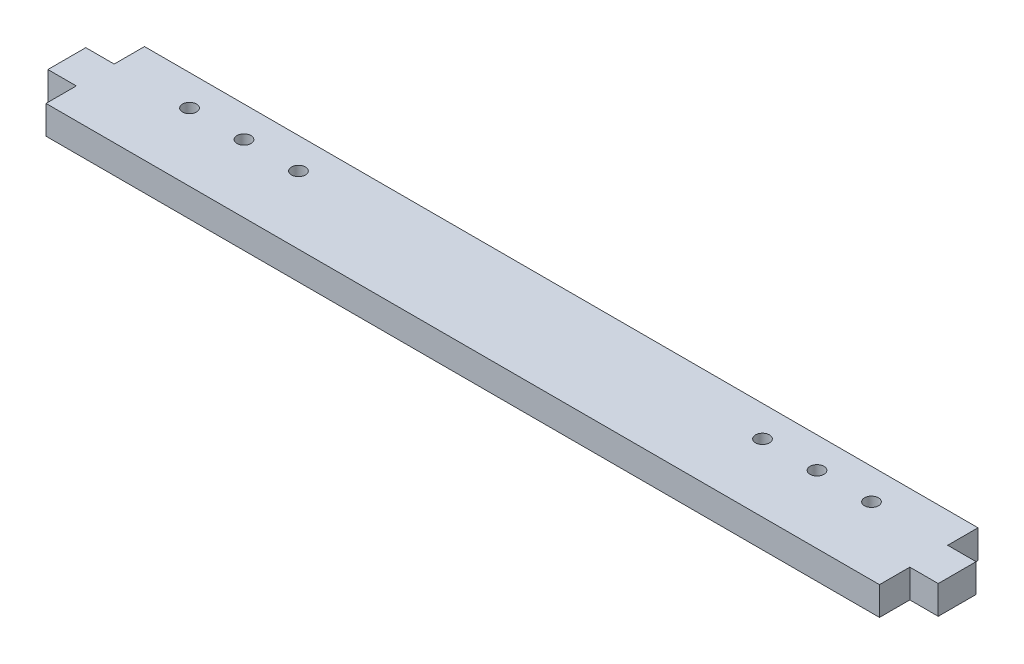
SolidWorks part; units mm, degrees
ref_plane "Front Plane" through (0, 0, 0) normal (0, 0, 1) x (1, 0, 0)
ref_plane "Top Plane" through (0, 0, 0) normal (0, 1, 0) x (1, 0, 0)
ref_plane "Right Plane" through (0, 0, 0) normal (1, 0, 0) x (0, 0, -1)
sketch "Sketch1" plane through (0, 0, 0) normal (0, 1, 0) x (1, 0, 0)
  line L1 (139.7, -16.51) -> (-139.7, -16.51)
  line L2 (139.7, -16.51) -> (139.7, 16.51)
  line L3 (139.7, 16.51) -> (-139.7, 16.51)
  line L4 (-139.7, -16.51) -> (-139.7, 16.51)
  line L5 (139.7, -16.51) -> (-139.7, 16.51) construction
  line L6 (139.7, 16.51) -> (-139.7, -16.51) construction
  point P0 (0, 0)
  dimension "D1" = 279.4
  dimension "D2" = 33.02
extrude "Boss-Extrude1" add sketch "Sketch1" along normal blind 9.525
sketch "Sketch2" plane through (139.7, 0, 0) normal (1, 0, 0) x (0, 0, -1)
  line L0 (-16.51, 0) -> (16.51, 0) construction
  line L1 (-6.35, 0) -> (6.35, 0)
  line L2 (-6.35, 0) -> (-6.35, 9.525)
  line L3 (-6.35, 9.525) -> (6.35, 9.525)
  line L4 (6.35, 0) -> (6.35, 9.525)
  line L5 (-16.51, 9.525) -> (16.51, 9.525) construction
  line L6 (-16.51, 9.525) -> (-16.51, 0) construction
  dimension "D1" = 12.7
  dimension "D2" = 10.16
extrude "Boss-Extrude2" add sketch "Sketch2" along normal blind 9.525
mirror "Mirror1" about plane through (0, 0, 0) normal (1, 0, 0) of "Boss-Extrude2"
sketch "Sketch3" plane through (0, 0, 0) normal (0, -1, 0) x (1, 0, 0)
  line L0 (139.7, -6.35) -> (139.7, -16.51) construction
  line L1 (139.7, -16.51) -> (-139.7, -16.51) construction
  line L2 (114.3, -16.51) -> (77.7748, -16.51) construction
  line L3 (114.3, -16.51) -> (114.3, -6.1976) construction
  line L4 (114.3, -6.1976) -> (77.7748, -6.1976) construction
  line L5 (77.7748, -16.51) -> (77.7748, -6.1976) construction
  line L6 (114.3, -16.51) -> (77.7748, -6.1976) construction
  line L7 (114.3, -6.1976) -> (77.7748, -16.51) construction
  circle A0 centre (114.3, -6.1976) radius 2.3368
  circle A1 centre (77.7748, -6.1976) radius 2.3368
  circle A2 centre (96.0374, -6.1976) radius 2.3368
  point P6 (96.0374, -11.3538)
  dimension "D4" = 4.6736
  dimension "D5" = 4.6736
  dimension "D6" = 4.6736
  dimension "D1" = 36.5252
  dimension "D2" = 10.3124
  dimension "D3" = 25.4
extrude "Cut-Extrude1" cut sketch "Sketch3" against normal through all
mirror "Mirror2" about plane through (0, 0, 0) normal (1, 0, 0) of "Cut-Extrude1"
